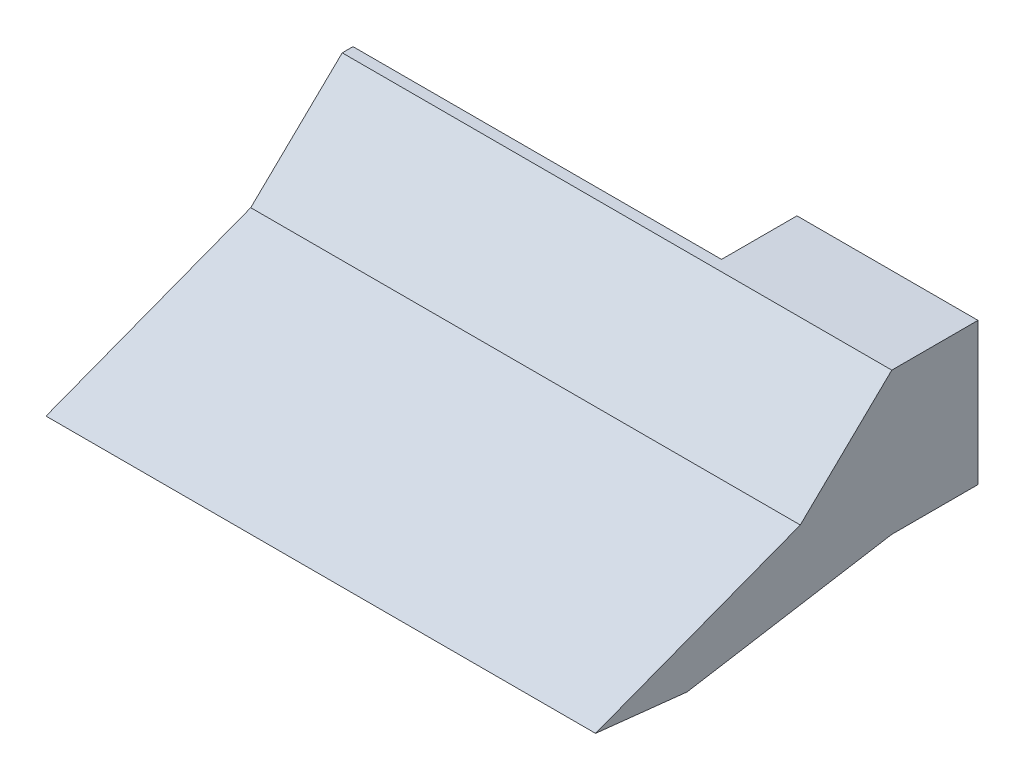
SolidWorks part; units mm, degrees
ref_plane "Front" through (0, 0, 0) normal (0, 0, 1) x (1, 0, 0)
ref_plane "Top" through (0, 0, 0) normal (0, 1, 0) x (1, 0, 0)
ref_plane "Right" through (0, 0, 0) normal (1, 0, 0) x (0, 0, -1)
sketch "Side base sketch" plane through (0, 0, 0) normal (-1, 0, 0) x (0, 0, 1)
  line L0 (0, 13.2) -> (8.4913, 5)
  line L1 (0, 0) -> (6, -1)
  line L2 (6, -1) -> (19, -3.1667)
  line L3 (8.4913, 5) -> (19.4913, 0.803)
  line L4 (19.4913, 0.803) -> (27.4913, -2.2493)
  line L5 (27.4913, -2.2493) -> (19, -3.1667)
  line L6 (0, 13.2) -> (0, 0)
  dimension "D1" = 6
  dimension "D2" = 6
  dimension "D3" = 1
  dimension "D4" = 46
  dimension "D5" = 13
  dimension "D6" = 11
  dimension "D7" = 4
  dimension "D8" = 8
  dimension "D9" = 13.2
extrude "Side base" add sketch "Side base sketch" against normal blind 1
pattern_linear "Side base 2" count 2 spacing 50 along (1, 0, 0) of bodies 108
sketch "Wall base sketch" plane through (1, 0, 0) normal (1, 0, 0) x (0, 0, -1)
  line L0 (0, 11.8098) -> (-7.9438, 4.1386)
  line L1 (-7.9438, 4.1386) -> (-25.3051, -2.4855)
  line L3 (-19, -3.4019) -> (-19, 4.6777) construction
  line L4 (0, 13.2) -> (0, 0) construction
  line L5 (0, 0) -> (-19, -3.1667) construction
  line L8 (-8.4913, 5) -> (0, 13.2) construction
  line L9 (0, 1.0138) -> (-19, -2.1529)
  line L11 (-19, -2.1529) -> (-19, -3.1667)
  line L12 (-19, -3.1667) -> (0, 0)
  line L13 (0, 0) -> (0, 1.0138)
  line L14 (-25.3051, -2.4855) -> (-27.4913, -2.2493)
  line L15 (-27.4913, -2.2493) -> (-8.4913, 5)
  line L16 (-8.4913, 5) -> (0, 13.2)
  line L17 (0, 13.2) -> (0, 11.8098)
  line L18 (-19, -3.1667) -> (-27.4913, -2.2493) construction
  dimension "D1" = 1
  dimension "D2" = 1
  dimension "D3" = 1
extrude "Front back walls" add sketch "Wall base sketch" along normal up to next
sketch "Base sketch" plane through (0, 0, 0) normal (0, 0, -1) x (-1, 0, 0)
  line L0 (-50, 11.8098) -> (-1, 11.8098) construction
  line L1 (0, 13.2) -> (-51, 13.2)
  line L2 (0, 13.2) -> (0, 0)
  line L3 (0, 0) -> (-51, 0)
  line L4 (-51, 13.2) -> (-51, 0)
  line L5 (-50, 1.0138) -> (-35.2, 1.0138)
  line L6 (-50, 1.0138) -> (-50, 11.8098)
  line L7 (-50, 11.8098) -> (-35.2, 11.8098)
  line L8 (-35.2, 1.0138) -> (-35.2, 11.8098)
  dimension "D1" = 14.8
extrude "Base" add sketch "Base sketch" along normal blind 1
sketch "Attachment base sketch" plane through (0, 0, -1) normal (0, 0, -1) x (-1, 0, 0)
  line L0 (-51, 0) -> (0, 0) construction
  line L1 (-51, 13.2) -> (-34.2, 13.2)
  line L2 (-51, 13.2) -> (-51, 0)
  line L3 (-51, 0) -> (-34.2, 0)
  line L4 (-34.2, 13.2) -> (-34.2, 0)
  line L5 (-35.2, 1.0138) -> (-35.2, 11.8098) construction
  line L7 (-35.2, 11.8098) -> (-50, 11.8098)
  line L8 (-35.2, 11.8098) -> (-35.2, 1.0138)
  line L9 (-35.2, 1.0138) -> (-50, 1.0138)
  line L10 (-50, 11.8098) -> (-50, 1.0138)
  dimension "D1" = 1
extrude "Attachment base" add sketch "Attachment base sketch" along normal blind 7
equation "\"wall_thicknes\"= 1"
equation "\"D1@Base\" = \"wall_thicknes\""
equation "\"D1@Wall base sketch\"=\"wall_thicknes\""
equation "\"D1@Side base\"=\"wall_thicknes\""
equation "\"D2@Wall base sketch\"=\"wall_thicknes\""
equation "\"D3@Wall base sketch\"=\"wall_thicknes\""
equation "\"D1@Base sketch\"=\"wall_thicknes\"*-2+16.8"
equation "\"D1@Attachment base sketch\"=\"wall_thicknes\""
